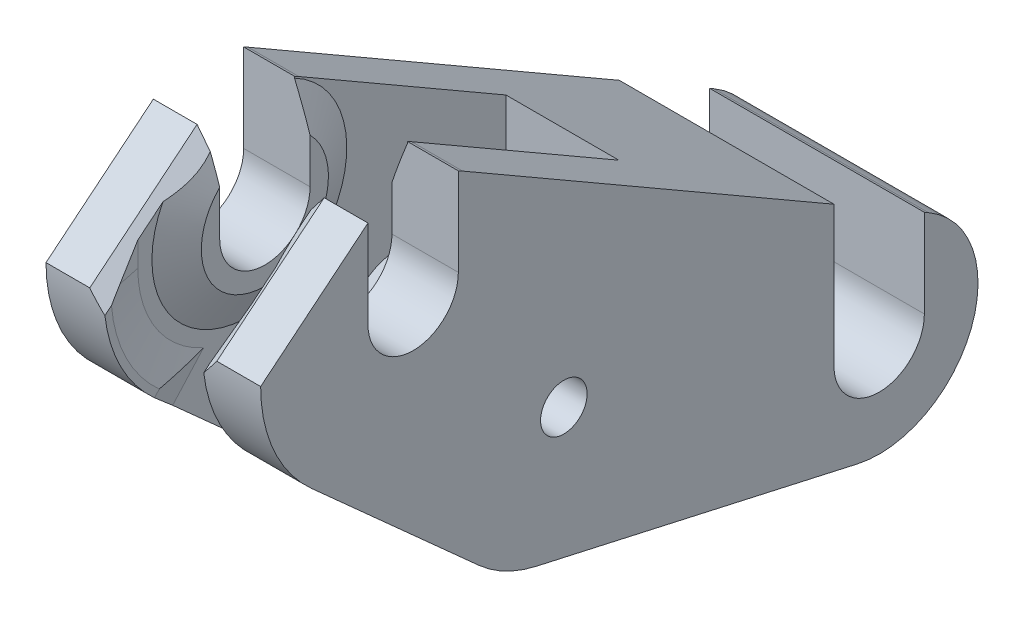
SolidWorks part; units mm, degrees
ref_plane "Front Plane" through (0, 0, 0) normal (0, 0, 1) x (1, 0, 0)
ref_plane "Top Plane" through (0, 0, 0) normal (0, 1, 0) x (1, 0, 0)
ref_plane "Right Plane" through (0, 0, 0) normal (1, 0, 0) x (0, 0, -1)
ref_plane "Plane4" through (15.2, 0, 0) normal (1, 0, 0) x (0, 0, -1)
ref_plane "Plane5" through (7.6, 0, 0) normal (1, 0, 0) x (0, 0, -1)
sketch "Sketch1" plane through (15.2, 0, 0) normal (1, 0, 0) x (0, 0, -1)
  line L0 (3.5235, 220.1706) -> (3.2238, 220.3437)
  line L1 (-32.977, 233.1595) -> (-32.9759, 206.2902) construction
  line L2 (-29.777, 233.1595) -> (-29.777, 239.3852)
  line L4 (-24.2736, 212.3771) -> (-1.5062, 207.2776)
  line L5 (-36.177, 233.1595) -> (-36.177, 239.3852)
  line L6 (3.2238, 214.1083) -> (3.2238, 220.3437)
  line L7 (-3.1762, 214.1083) -> (-3.1762, 224.0384)
  line L8 (-3.1762, 224.0384) -> (-29.4773, 239.2218)
  line L10 (-40.1924, 225.1235) -> (-28.3194, 214.4628)
  line L11 (-36.177, 239.3852) -> (-43.777, 233.1595)
  arc A1 (3.2238, 214.1083) -> (-3.1762, 214.1083) centre (0.0238, 214.1083) cw
  arc A2 (-29.777, 233.1595) -> (-36.177, 233.1595) centre (-32.977, 233.1595) cw
  arc A3 (-1.5062, 207.2776) -> (3.5235, 220.1706) centre (0.0238, 214.1083) ccw
  arc A4 (-29.4773, 239.2218) -> (-29.777, 239.3852) centre (-32.977, 233.1595) ccw
  arc A5 (-43.777, 233.1595) -> (-40.1924, 225.1235) centre (-32.977, 233.1595) ccw
  circle A6 centre (-22.3065, 221.1595) radius 1.65
  arc A7 (-28.3194, 214.4628) -> (-24.2736, 212.3771) centre (-22.3065, 221.1595) ccw
  dimension "D1" = 3.3
  dimension "D2" = 6.4
  dimension "D3" = 7
  dimension "D8" = 9
  dimension "D9" = 21.6
  dimension "D4" = 38.1051
  dimension "D5" = 60
  dimension "D6" = 10.67
  dimension "D7" = 12
extrude "Boss-Extrude1" add sketch "Sketch1" against normal blind 15.2
ref_axis "Axis1" through (0, 214.1083, -0.0238) along (1, 0, 0)
sketch "Sketch4" plane through (7.6, 0, 0) normal (1, 0, 0) x (0, 0, -1)
  line L0 (-29.1899, 216.7511) -> (-26.4931, 214.9367)
  line L1 (-14.8065, 221.1595) -> (-14.8065, 244.6595)
  line L2 (-14.8065, 244.6595) -> (-32.977, 244.6595)
  line L3 (-39.3964, 223.6179) -> (-31.91, 213.7167)
  line L4 (-31.91, 213.7167) -> (-29.1899, 216.7511)
  arc A0 (-26.4931, 214.9367) -> (-14.8065, 221.1595) centre (-22.3065, 221.1595) ccw
  circle A1 centre (-22.3065, 221.1595) radius 1.65 construction
  circle A2 centre (-22.3065, 221.1595) radius 5 construction
  circle A3 centre (-32.977, 233.1595) radius 9.5 construction
  arc A4 (-32.977, 244.6595) -> (-39.3964, 223.6179) centre (-32.977, 233.1595) ccw
  dimension "D1" = 2.5
  dimension "D2" = 19
  dimension "D3" = 10
  dimension "D4" = 2
extrude "Cut-Extrude2" cut sketch "Sketch4" against normal blind 4 and the other way blind 4
sketch "Sketch6" plane through (3.6, 0, 0) normal (1, 0, 0) x (0, 0, -1)
  circle A0 centre (-22.3065, 221.1595) radius 2.6
  circle A1 centre (-22.3065, 221.1595) radius 1.65
  dimension "D1" = 5.2
extrude "Boss-Extrude4" add sketch "Sketch6" along normal blind 2.3
sketch "Sketch7" plane through (3.6, 0, 0) normal (1, 0, 0) x (0, 0, -1)
  line L0 (-36.177, 233.1595) -> (-36.177, 236.3233)
  line L1 (-43.277, 233.1595) -> (-43.277, 233.5691)
  line L2 (-29.777, 236.3233) -> (-29.777, 233.1595)
  line L3 (-39.8584, 225.4955) -> (-40.1924, 225.1235)
  line L5 (-43.277, 233.5691) -> (-43.777, 233.1595)
  line L6 (-36.177, 239.3852) -> (-43.777, 233.1595) construction
  line L13 (-25.3871, 216.2452) -> (-26.29, 214.8048)
  line L14 (-16.5065, 221.1595) -> (-14.8065, 221.1595)
  arc A0 (-36.177, 233.1595) -> (-29.777, 233.1595) centre (-32.977, 233.1595) ccw
  arc A1 (-36.177, 236.3233) -> (-29.777, 236.3233) centre (-32.977, 233.1595) ccw
  arc A2 (-43.777, 233.1595) -> (-40.1924, 225.1235) centre (-32.977, 233.1595) ccw
  arc A3 (-43.277, 233.1595) -> (-39.8584, 225.4955) centre (-32.977, 233.1595) ccw
  arc A4 (-26.29, 214.8048) -> (-14.8065, 221.1595) centre (-22.3065, 221.1595) ccw
  arc A5 (-25.3871, 216.2452) -> (-16.5065, 221.1595) centre (-22.3065, 221.1595) ccw
  dimension "D1" = 4.5
  dimension "D2" = 10.3
  dimension "D3" = 11.6
  dimension "D4" = 15
extrude "Boss-Extrude5" add sketch "Sketch7" along normal blind 0.5
sketch "Sketch12" plane through (4.1, 0, 0) normal (1, 0, 0) x (0, 0, -1)
  line L2 (-36.177, 233.1595) -> (-36.177, 236.3233)
  line L3 (-29.777, 236.3233) -> (-29.777, 233.1595)
  line L4 (-36.177, 233.1595) -> (-36.177, 236.3233)
  line L5 (-29.777, 236.3233) -> (-29.777, 233.1595)
  arc A2 (-36.177, 233.1595) -> (-29.777, 233.1595) centre (-32.977, 233.1595) ccw
  arc A3 (-36.177, 236.3233) -> (-29.777, 236.3233) centre (-32.977, 233.1595) ccw
  arc A4 (-36.177, 233.1595) -> (-29.777, 233.1595) centre (-32.977, 233.1595) ccw
  arc A5 (-36.177, 236.3233) -> (-29.777, 236.3233) centre (-32.977, 233.1595) ccw
  dimension "D1" = 0
extrude "Boss-Extrude6" add sketch "Sketch12" along normal blind 0.3
sketch "Sketch13" plane through (4.4, 0, 0) normal (1, 0, 0) x (0, 0, -1)
  line L2 (-36.177, 233.1595) -> (-36.177, 236.3233)
  line L3 (-29.777, 236.3233) -> (-29.777, 233.1595)
  line L4 (-36.177, 233.1595) -> (-36.177, 236.3233)
  line L5 (-29.777, 236.3233) -> (-29.777, 233.1595)
  arc A2 (-36.177, 233.1595) -> (-29.777, 233.1595) centre (-32.977, 233.1595) ccw
  arc A3 (-36.177, 236.3233) -> (-29.777, 236.3233) centre (-32.977, 233.1595) ccw
  arc A4 (-36.177, 233.1595) -> (-29.777, 233.1595) centre (-32.977, 233.1595) ccw
  arc A5 (-36.177, 236.3233) -> (-29.777, 236.3233) centre (-32.977, 233.1595) ccw
  dimension "D1" = 0
extrude "Boss-Extrude8" add sketch "Sketch13" along normal blind 0.3 contours A5 L5 A4 L4
chamfer "Chamfer4" distance 2.4 distance2 1.1 1 edges at (3.6, 228.6595, 32.977) first distance on face at (3.6, 221.1595, 19.7065)
chamfer "Chamfer6" distance 2.4 distance2 0.5 3 edges at (3.6, 233.3643, 43.277) (3.6, 228.9635, 42.3836) (3.6, 225.3095, 40.0254) first distance on face at (3.6, 221.1595, 19.7065)
mirror "Mirror3" about plane through (7.6, 0, 0) normal (1, 0, 0) of "Boss-Extrude8", "Boss-Extrude6", "Boss-Extrude5", "Boss-Extrude4"
chamfer "Chamfer7" distance 1.4 distance2 0.5 3 edges at (3.6, 216.0847, 19.4983) (3.6, 221.1595, 15.6565) (3.6, 215.525, 25.8386) first distance on face at (3.6, 225.6337, 29.0244)
chamfer "Chamfer8" distance 1.4 distance2 2.3 1 edges at (3.6, 221.1595, 19.7065) first distance on face at (3.6, 226.6912, 29.3809)
chamfer "Chamfer9" distance 1.1 distance2 2.4 1 edges at (11.6, 228.6595, 32.977) first distance on face at (11.05, 232.4914, 32.977)
chamfer "Chamfer10" distance 0.5 distance2 2.4 3 edges at (11.6, 233.3643, 43.277) (11.6, 225.3095, 40.0254) (11.6, 228.9635, 42.3836) first distance on face at (11.35, 233.3643, 43.277) first distance on face at (11.35, 225.3095, 40.0254) first distance on face at (11.35, 229.1455, 41.9757)
chamfer "Chamfer11" distance 2.3 distance2 1.4 1 edges at (11.6, 221.1595, 19.7065) first distance on face at (9.3, 221.1595, 19.7065)
chamfer "Chamfer12" distance 0.5 distance2 1.4 3 edges at (11.6, 221.1595, 15.6565) (11.6, 216.0847, 19.4983) (11.6, 215.525, 25.8386) first distance on face at (11.35, 221.1595, 15.6565) first distance on face at (11.35, 217.3935, 20.2225) first distance on face at (11.35, 215.525, 25.8386)
chamfer "Chamfer13" distance 1 distance2 1 2 edges at (11.1, 233.3643, 43.527) (4.1, 233.3643, 43.527)
sketch "Sketch8" plane through (3.6, 0, 0) normal (1, 0, 0) x (0, 0, -1)
  line L1 (-72.3716, 261.826) -> (29.6064, 261.826)
  line L2 (-72.3716, 261.826) -> (-72.3716, 195.9976)
  line L3 (-72.3716, 195.9976) -> (29.6064, 195.9976)
  line L4 (29.6064, 261.826) -> (29.6064, 195.9976)
  line L5 (-72.3716, 261.826) -> (29.6064, 195.9976) construction
  line L6 (-72.3716, 195.9976) -> (29.6064, 261.826) construction
  point P0 (-21.3826, 228.9118)
extrude "Cut-Extrude3" [suppressed] cut sketch "Sketch8" against normal blind 10
sketch "Sketch9" [suppressed] plane through (3.6, 0, 0) normal (-1, 0, 0) x (0, 0, 1)
  line L0 (38.4067, 223.52) -> (40.1924, 225.1235) construction
  line L1 (43.7586, 232.5283) -> (40.877, 234.8888) construction
  line L2 (40.877, 234.8888) -> (40.877, 233.1595) construction
  line L3 (36.2197, 225.9557) -> (38.4067, 223.52) construction
  line L4 (39.0965, 236.3474) -> (36.177, 238.7389) construction
  line L5 (36.177, 238.7389) -> (36.177, 233.1595) construction
  line L6 (29.777, 233.1595) -> (29.777, 239.2726) construction
  line L9 (38.4067, 223.52) -> (40.1924, 225.1235)
  line L10 (43.7586, 232.5283) -> (40.877, 234.8888)
  line L11 (40.877, 234.8888) -> (40.877, 233.1595)
  line L12 (36.2197, 225.9557) -> (38.4067, 223.52)
  line L13 (39.0965, 236.3474) -> (36.177, 238.7389)
  line L14 (36.177, 238.7389) -> (36.177, 233.1595)
  line L15 (29.777, 233.1595) -> (29.777, 239.2726)
  line L17 (26.29, 214.8048) -> (27.4543, 215.5834)
  line L18 (14.8065, 221.1595) -> (14.8065, 222.5595)
  line L19 (14.8065, 222.5595) -> (18.1352, 222.5595)
  line L20 (27.4543, 215.5834) -> (25.7083, 218.3688)
  arc A0 (40.1924, 225.1235) -> (43.7586, 232.5283) centre (32.977, 233.1595) ccw construction
  arc A1 (36.2197, 225.9557) -> (40.877, 233.1595) centre (32.977, 233.1595) ccw construction
  arc A2 (29.777, 233.1595) -> (36.177, 233.1595) centre (32.977, 233.1595) ccw construction
  arc A3 (29.777, 239.2726) -> (39.0965, 236.3474) centre (32.977, 233.1595) ccw construction
  circle A4 centre (22.3065, 221.1595) radius 4 construction
  arc A5 (14.8065, 221.1595) -> (26.29, 214.8048) centre (22.3065, 221.1595) ccw construction
  arc A6 (18.1352, 222.5595) -> (25.7083, 218.3688) centre (22.3065, 221.1595) ccw construction
  arc A7 (40.1924, 225.1235) -> (43.7586, 232.5283) centre (32.977, 233.1595) ccw
  arc A8 (36.2197, 225.9557) -> (40.877, 233.1595) centre (32.977, 233.1595) ccw
  arc A9 (29.777, 233.1595) -> (36.177, 233.1595) centre (32.977, 233.1595) ccw
  arc A10 (29.777, 239.2726) -> (39.0965, 236.3474) centre (32.977, 233.1595) ccw
  circle A11 centre (22.3065, 221.1595) radius 4
  arc A12 (14.8065, 221.1595) -> (26.29, 214.8048) centre (22.3065, 221.1595) ccw
  arc A13 (18.1352, 222.5595) -> (25.7083, 218.3688) centre (22.3065, 221.1595) ccw
extrude "Cut-Extrude4" [suppressed] cut sketch "Sketch9" against normal up to next
sketch "Sketch10" [suppressed] plane through (5.6, 0, 0) normal (1, 0, 0) x (0, 0, -1)
  line L1 (21.8763, 154.7145) -> (-60.7425, 154.7145)
  line L2 (21.8763, 154.7145) -> (21.8763, 287.4356)
  line L3 (21.8763, 287.4356) -> (-60.7425, 287.4356)
  line L4 (-60.7425, 154.7145) -> (-60.7425, 287.4356)
  line L5 (21.8763, 154.7145) -> (-60.7425, 287.4356) construction
  line L6 (21.8763, 287.4356) -> (-60.7425, 154.7145) construction
  point P0 (-19.4331, 221.0751)
extrude "Cut-Extrude5" [suppressed] cut sketch "Sketch10" along normal blind 10
sketch "Sketch11" [suppressed] plane through (5.6, 0, 0) normal (1, 0, 0) x (0, 0, -1)
  line L8 (-3.1762, 224.0384) -> (-14.8065, 230.7525)
  line L9 (-14.8065, 230.7525) -> (-14.8065, 221.1595)
  line L10 (-26.4931, 214.9367) -> (-35.8833, 221.2544)
  line L11 (-35.8833, 221.2544) -> (-28.3194, 214.4628)
  line L12 (-24.2736, 212.3771) -> (-1.5062, 207.2776)
  line L13 (3.5235, 220.1706) -> (3.2238, 220.3437)
  line L14 (3.2238, 220.3437) -> (3.2238, 214.1083)
  line L15 (-3.1762, 214.1083) -> (-3.1762, 224.0384)
  line L16 (-3.1762, 224.0384) -> (-14.8065, 230.7525)
  line L17 (-14.8065, 230.7525) -> (-14.8065, 221.1595)
  line L18 (-26.4931, 214.9367) -> (-35.8833, 221.2544)
  line L19 (-35.8833, 221.2544) -> (-28.3194, 214.4628)
  line L20 (-24.2736, 212.3771) -> (-1.5062, 207.2776)
  line L21 (3.5235, 220.1706) -> (3.2238, 220.3437)
  line L22 (3.2238, 220.3437) -> (3.2238, 214.1083)
  line L23 (-3.1762, 214.1083) -> (-3.1762, 224.0384)
  arc A4 (-26.4931, 214.9367) -> (-14.8065, 221.1595) centre (-22.3065, 221.1595) ccw
  arc A5 (-28.3194, 214.4628) -> (-24.2736, 212.3771) centre (-22.3065, 221.1595) ccw
  arc A6 (-1.5062, 207.2776) -> (3.5235, 220.1706) centre (0.0238, 214.1083) ccw
  arc A7 (-3.1762, 214.1083) -> (3.2238, 214.1083) centre (0.0238, 214.1083) ccw
  arc A8 (-26.4931, 214.9367) -> (-14.8065, 221.1595) centre (-22.3065, 221.1595) ccw
  arc A9 (-28.3194, 214.4628) -> (-24.2736, 212.3771) centre (-22.3065, 221.1595) ccw
  arc A10 (-1.5062, 207.2776) -> (3.5235, 220.1706) centre (0.0238, 214.1083) ccw
  arc A11 (-3.1762, 214.1083) -> (3.2238, 214.1083) centre (0.0238, 214.1083) ccw
  dimension "D1" = 0
extrude "Cut-Extrude6" [suppressed] cut sketch "Sketch11" against normal up to surface (2 mm away)
chamfer "Chamfer14" [suppressed] distance 0.5 angle 45
chamfer "Chamfer15" [suppressed] distance 0.5 angle 45
chamfer "Chamfer16" [suppressed] distance 0.5 angle 45
